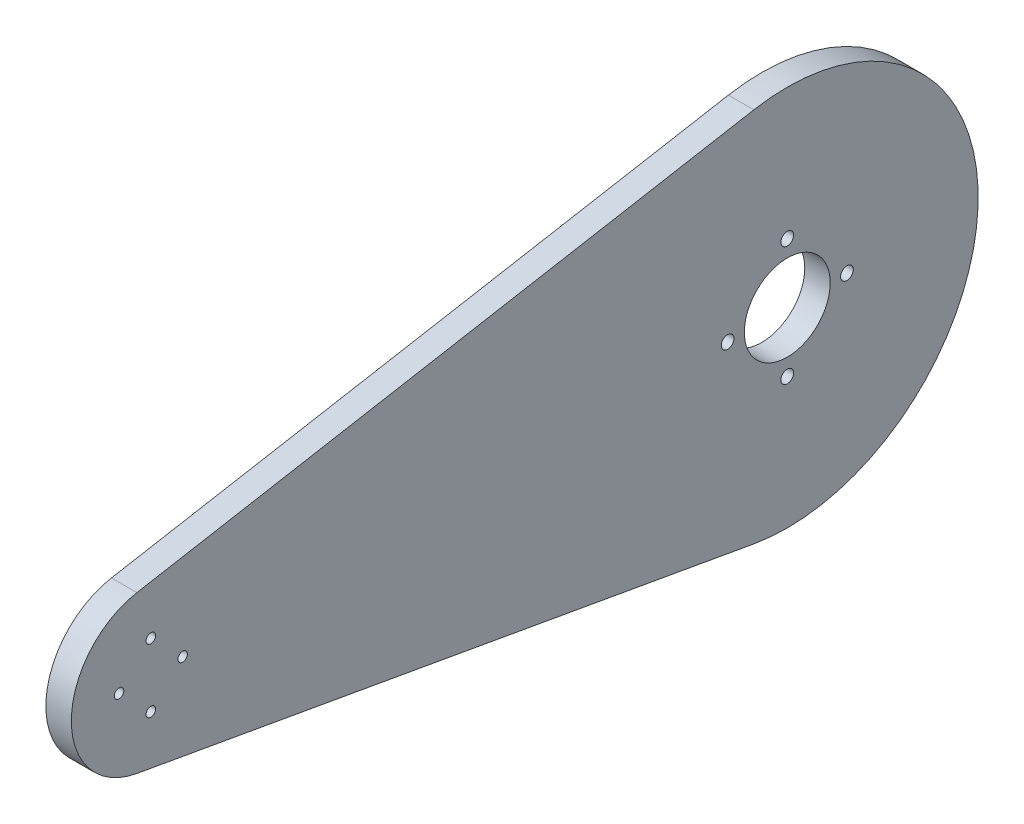
SolidWorks part; units mm, degrees
material "2024-T4"
ref_plane "Front Plane" through (0, 0, 0) normal (0, 0, 1) x (1, 0, 0)
ref_plane "Top Plane" through (0, 0, 0) normal (0, 1, 0) x (1, 0, 0)
ref_plane "Right Plane" through (0, 0, 0) normal (1, 0, 0) x (0, 0, -1)
sketch "Sketch1" plane through (0, 0, 0) normal (1, 0, 0) x (0, 0, -1)
  line L0 (0, 0) -> (-200, 0) construction
  line L1 (-204.375, 24.6142) -> (-10.5, 59.0741)
  line L2 (-204.375, -24.6142) -> (-10.5, -59.0741)
  circle A0 centre (0, 0) radius 13.5
  arc A1 (-10.5, -59.0741) -> (-10.5, 59.0741) centre (0, 0) ccw
  arc A2 (-204.375, 24.6142) -> (-204.375, -24.6142) centre (-200, 0) ccw
  dimension "D1" = 120
  dimension "D2" = 27
  dimension "D3" = 25
  dimension "D5" = 200
extrude "Boss-Extrude1" add sketch "Sketch1" along normal mid plane 8
sketch "Sketch2" plane through (4, 0, 0) normal (1, 0, 0) x (0, 0, -1)
  line L0 (0, 0) -> (0, 18.75) construction
  line L1 (-200, 0) -> (-210, 0) construction
  circle A0 centre (0, 18.75) radius 2
  circle A1 centre (18.75, 0) radius 2
  circle A2 centre (0, -18.75) radius 2
  circle A3 centre (-18.75, 0) radius 2
  circle A4 centre (-200, 0) radius 10 construction
  circle A5 centre (-210, 0) radius 1.5
  circle A6 centre (-200, 10) radius 1.5
  circle A7 centre (-190, 0) radius 1.5
  circle A8 centre (-200, -10) radius 1.5
  point P13 (0, 0)
  point P17 (-200, 10)
  point P18 (-200, -10)
  point P24 (-200, 0)
  point P25 (-210, 0)
  point P26 (-200, -10)
  dimension "D1" = 4
  dimension "D6" = 20
  dimension "D7" = 3
  dimension "D2" = 18.75
  dimension "D4" = 18.75
  dimension "D5" = 18.75
  dimension "D9" = 20
  dimension "D10" = 10
  dimension "D3" = 4
  dimension "D8" = 4
extrude "Cut-Extrude1" cut sketch "Sketch2" against normal through all
equation "\"D4@Sketch2\"=\"D2@Sketch2\""
equation "\"D5@Sketch2\"=\"D2@Sketch2\""
equation "\"shaft-diameter\"=20mm"
equation "\"key-length\"=12mm"
equation "\"key-width\"=4mm"
equation "\"flippershaft-wormgear-diameter\"= 35mm"
equation "\"shaft-ring-groove-depth\"=0.5mm"
equation "\"shaft-ring-groove-width\"= 1.3mm"
equation "\"mini-shaft-diameter\"= 12mm"
equation "\"mini-flipper-shaft-diameter\"= 26mm"
